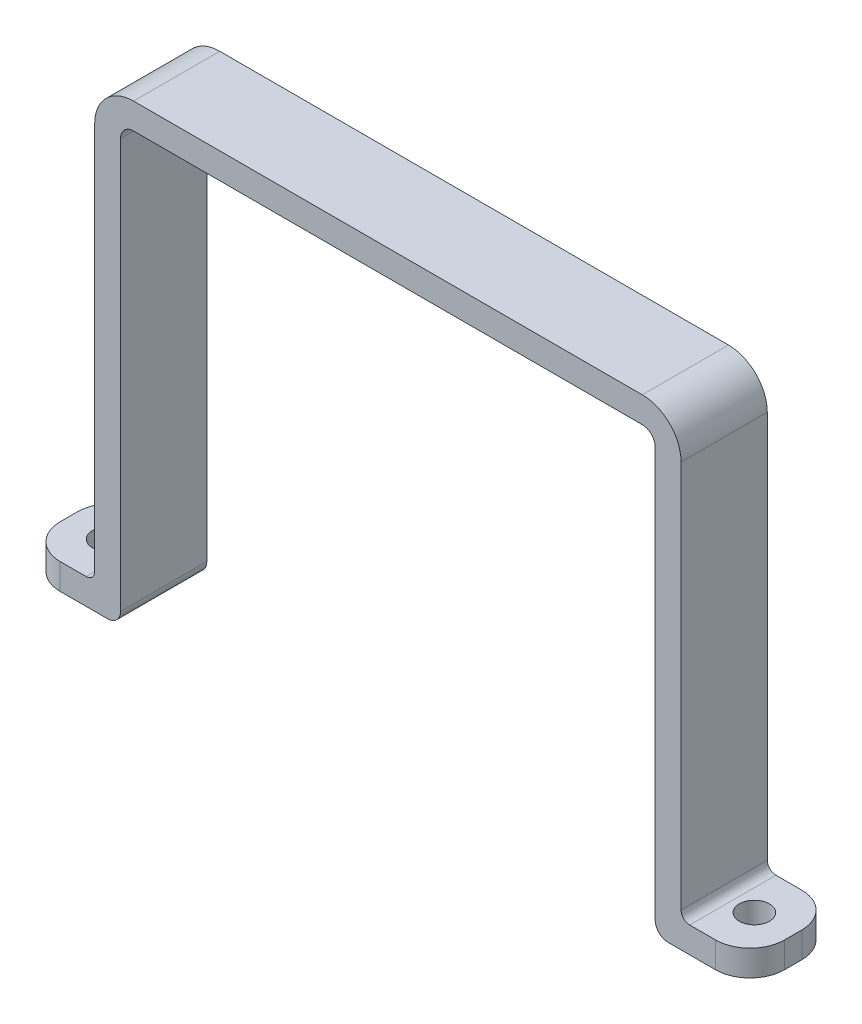
SolidWorks part; units mm, degrees
ref_plane "Alzado" through (0, 0, 0) normal (0, 0, 1) x (1, 0, 0)
ref_plane "Planta" through (0, 0, 0) normal (0, 1, 0) x (1, 0, 0)
ref_plane "Vista lateral" through (0, 0, 0) normal (1, 0, 0) x (0, 0, -1)
sketch "Croquis1" plane through (0, 0, 0) normal (0, 0, 1) x (1, 0, 0)
  line L0 (0, 0) -> (11, 0)
  line L1 (11, 0) -> (11, 50.5)
  line L2 (11, 50.5) -> (73, 50.5)
  line L3 (73, 50.5) -> (73, 0)
  line L4 (73, 0) -> (84, 0)
  line L5 (84, 0) -> (84, 3)
  line L6 (84, 3) -> (76, 3)
  line L7 (76, 3) -> (76, 53.5)
  line L8 (76, 53.5) -> (8, 53.5)
  line L9 (8, 53.5) -> (8, 3)
  line L10 (8, 3) -> (0, 3)
  line L11 (0, 3) -> (0, 0)
  dimension "D1" = 3
  dimension "D2" = 3
  dimension "D3" = 3
  dimension "D4" = 3
  dimension "D5" = 3
  dimension "D6" = 62
  dimension "D7" = 50.5
  dimension "D8" = 11
extrude "Saliente-Extruir1" add sketch "Croquis1" along normal mid plane 10
ref_plane "Plano1" through (42, 0, 0) normal (1, 0, 0) x (0, 0, -1)
fillet "Redondeo1" radius 4 4 edges at (0, 1.5, -5) (0, 1.5, 5) (84, 1.5, -5) (84, 1.5, 5)
sketch "Croquis2" plane through (0, 3, 0) normal (0, 1, 0) x (1, 0, 0)
  line L1 (84, -1) -> (84, 1) construction
  line L2 (80, -5) -> (76, -5) construction
  circle A0 centre (79.5, 0) radius 1.75
  point P3 (0, 0)
  dimension "D1" = 3.5
  dimension "D2" = 4.5
  dimension "D3" = 5
extrude "Cortar-Extruir1" cut sketch "Croquis2" against normal through all
mirror "Simetría1" about plane through (42, 0, 0) normal (1, 0, 0) of "Cortar-Extruir1"
fillet "Redondeo2" radius 1.5 2 edges at (11, 50.5, 0) (73, 50.5, 0)
fillet "Redondeo3" radius 4.5 2 edges at (76, 53.5, 0) (8, 53.5, 0)
fillet "Redondeo4" radius 1.5 2 edges at (73, 0, 0) (11, 0, 0)
fillet "Redondeo5" radius 1 2 edges at (76, 3, 0) (8, 3, 0)
